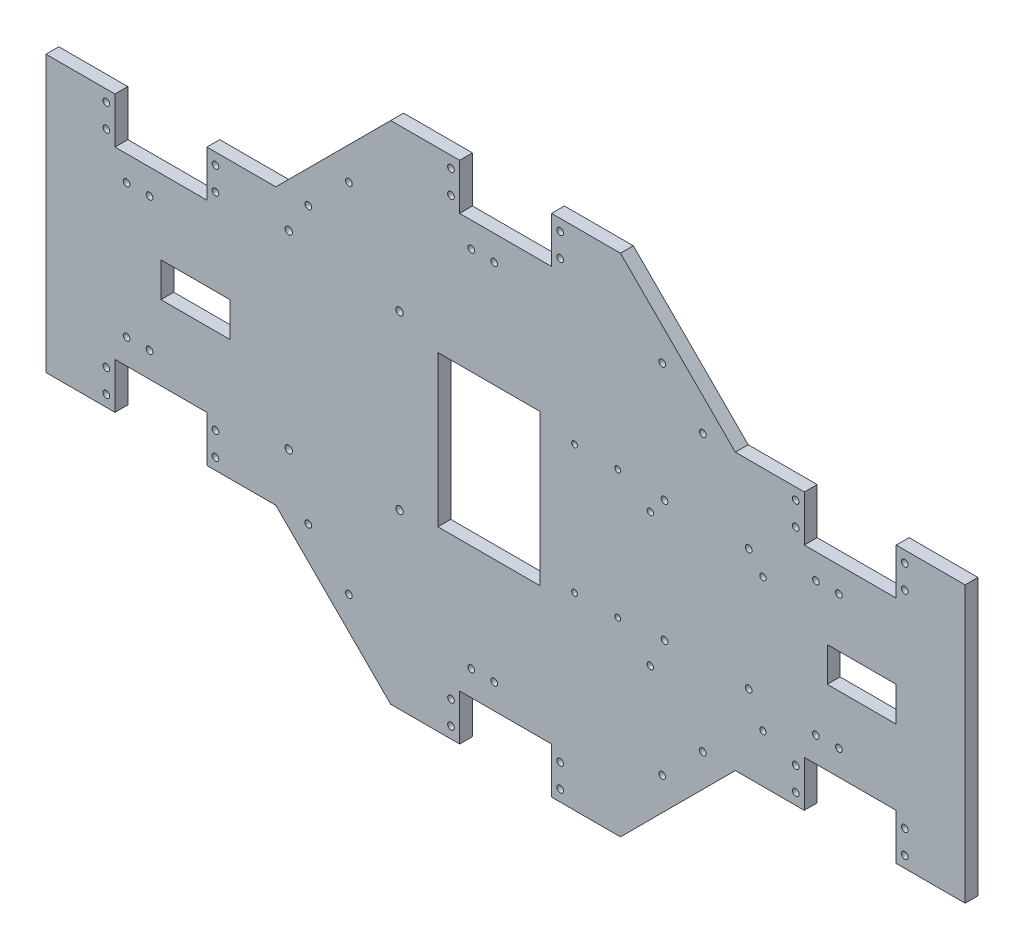
SolidWorks part; units mm, degrees
ref_plane "Front" through (0, 0, 0) normal (0, 0, 1) x (1, 0, 0)
ref_plane "Top" through (0, 0, 0) normal (0, 1, 0) x (1, 0, 0)
ref_plane "Right" through (0, 0, 0) normal (1, 0, 0) x (0, 0, -1)
sketch "Esquisse1" plane through (0, 0, 0) normal (0, 0, 1) x (1, 0, 0)
  line L0 (100, -60) -> (150, -110)
  line L1 (0, 0) -> (25.8386, 0)
  line L2 (0, 0) -> (0, -60)
  line L3 (0, -60) -> (100, -60)
  line L5 (0, 0) -> (100, -60) construction
  line L6 (0, -60) -> (25.8386, 0) construction
  line L7 (150, -110) -> (250, -110)
  line L8 (250, -110) -> (300, -60)
  line L9 (300, -60) -> (400, -60)
  line L10 (400, -60) -> (400, 0)
  line L11 (400, 0) -> (25.8386, 0)
  point P0 (0, 0)
  dimension "D1" = 100
  dimension "D2" = 100
  dimension "D3" = 100
  dimension "D4" = 135
  dimension "D5" = 135
  dimension "D6" = 0
  dimension "D7" = 50
  dimension "D8" = 60
extrude "Boss.-Extru.1" add sketch "Esquisse1" along normal blind 5.6
sketch "Esquisse2" plane through (0, 0, 5.6) normal (0, 0, 1) x (1, 0, 0)
  line L0 (0, -60) -> (100, -60) construction
  line L1 (30, -40) -> (70, -40)
  line L2 (30, -40) -> (30, -60)
  line L3 (30, -60) -> (70, -60)
  line L4 (70, -40) -> (70, -60)
  line L5 (30, -40) -> (70, -60) construction
  line L6 (30, -60) -> (70, -40) construction
  line L7 (0, 0) -> (0, -60) construction
  point P0 (0, -90)
  dimension "D1" = 20
  dimension "D2" = 40
  dimension "D3" = 30
extrude "Enlèv. mat.-Extru.1" cut sketch "Esquisse2" against normal up to next
sketch "Esquisse3" plane through (0, 0, 5.6) normal (0, 0, 1) x (1, 0, 0)
  line L0 (30, -50) -> (70, -50) construction
  line L1 (30, -40) -> (30, -60) construction
  line L2 (70, -60) -> (70, -40) construction
  circle A0 centre (26.25, -55.08) radius 1.45
  circle A1 centre (73.75, -55.08) radius 1.45
  circle A2 centre (73.75, -44.92) radius 1.45
  circle A3 centre (26.25, -44.92) radius 1.45
  circle A4 centre (35.06, -29.09) radius 1.45
  circle A5 centre (45.06, -29.09) radius 1.45
  dimension "D1" = 3.75
  dimension "D2" = 5.08
  dimension "D3" = 47.5
  dimension "D4" = 2.9
  dimension "D5" = 3.75
  dimension "D6" = 2.9
  dimension "D7" = 2.9
  dimension "D8" = 10
  dimension "D9" = 8.81
  dimension "D10" = 15.83
  dimension "D11" = 0
extrude "Enlèv. mat.-Extru.2" cut sketch "Esquisse3" against normal up to next
sketch "Sketch2" plane through (0, 0, 0) normal (0, 0, 1) x (1, 0, 0)
  line L0 (150, -110) -> (250, -110) construction
  line L1 (330, -40) -> (370, -40)
  line L2 (330, -40) -> (330, -60)
  line L3 (330, -60) -> (370, -60)
  line L4 (370, -40) -> (370, -60)
  line L5 (330, -40) -> (370, -60) construction
  line L6 (330, -60) -> (370, -40) construction
  line L7 (300, -60) -> (400, -60) construction
  line L8 (400, -60) -> (400, 0) construction
  line L9 (180, -90) -> (220, -90)
  line L10 (180, -90) -> (180, -110)
  line L11 (180, -110) -> (220, -110)
  line L12 (220, -90) -> (220, -110)
  line L13 (180, -90) -> (220, -110) construction
  line L14 (180, -110) -> (220, -90) construction
  point P0 (0, -90)
  point P11 (-35, 0)
  dimension "D1" = 20
  dimension "D2" = 40
  dimension "D3" = 30
  dimension "D4" = 40
  dimension "D5" = 20
  dimension "D6" = 30
extrude "Cut-Extrude2" cut sketch "Sketch2" against normal through all and the other way through all
sketch "Sketch5" plane through (0, 0, 0) normal (0, 0, 1) x (1, 0, 0)
  line L0 (180, -100) -> (220, -100) construction
  line L1 (220, -110) -> (220, -90) construction
  line L2 (330, -50) -> (370, -50) construction
  line L4 (370, -60) -> (370, -40) construction
  line L5 (330, -40) -> (330, -60) construction
  circle A0 centre (176.25, -105.08) radius 1.45
  circle A1 centre (223.75, -105.08) radius 1.45
  circle A2 centre (223.75, -94.92) radius 1.45
  circle A3 centre (176.25, -94.92) radius 1.45
  circle A4 centre (326.25, -55.08) radius 1.45
  circle A5 centre (373.75, -55.08) radius 1.45
  circle A6 centre (373.75, -44.92) radius 1.45
  circle A7 centre (326.25, -44.92) radius 1.45
  circle A8 centre (185.06, -79.09) radius 1.45
  circle A9 centre (195.06, -79.09) radius 1.45
  circle A10 centre (335.06, -29.09) radius 1.45
  circle A11 centre (345.06, -29.09) radius 1.45
  dimension "D1" = 5.08
  dimension "D2" = 5.08
  dimension "D3" = 47.5
  dimension "D4" = 2.9
  dimension "D5" = 3.75
  dimension "D10" = 2.9
  dimension "D11" = 2.9
  dimension "D12" = 2.9
  dimension "D16" = 2.9
  dimension "D17" = 2.9
  dimension "D6" = 5.08
  dimension "D7" = 5.08
  dimension "D8" = 3.75
  dimension "D9" = 3.75
  dimension "D13" = 10
  dimension "D14" = 8.81
  dimension "D15" = 15.83
  dimension "D18" = 8.81
  dimension "D19" = 15.83
  dimension "D20" = 10
  dimension "D21" = 0
  dimension "D22" = 0
extrude "Cut-Extrude4" cut sketch "Sketch5" along normal through all
mirror "Mirror1" about plane through (0, 0, 0) normal (0, 1, 0) of "Cut-Extrude4", "Cut-Extrude2", "Enlèv. mat.-Extru.1", "Enlèv. mat.-Extru.2", "Boss.-Extru.1"
sketch "Esquisse4" plane through (0, 0, 5.6) normal (0, 0, 1) x (1, 0, 0)
  circle A0 centre (263, -39) radius 1.375
  circle A4 centre (312, -39) radius 1.375
  circle A5 centre (312, 19) radius 1.375
  circle A6 centre (263, 19) radius 1.375
  dimension "D1" = 2.75
  dimension "D2" = 2
  dimension "D3" = 43
  dimension "D4" = 51
  dimension "D5" = 2
extrude "Enlèv. mat.-Extru.4" cut sketch "Esquisse4" against normal through all
sketch "Esquisse6" plane through (0, 0, 0) normal (0, 0, -1) x (-1, 0, 0)
  circle A0 centre (-269.19, -26.31) radius 1.45
  circle A4 centre (-305.82, -26.31) radius 1.45
  circle A5 centre (-305.82, 26.52) radius 1.45
  circle A6 centre (-269.19, 26.52) radius 1.45
  dimension "D1" = 2.9
  dimension "D2" = 2
  dimension "D3" = 63.69
  dimension "D4" = 49.19
  dimension "D5" = 2
extrude "Enlèv. mat.-Extru.6" cut sketch "Esquisse6" against normal through all
sketch "Esquisse8" plane through (0, 0, 0) normal (0, 0, -1) x (-1, 0, 0)
  circle A0 centre (-230, 27.95) radius 1.25
  circle A1 centre (-248.8, 27.95) radius 1.25
  circle A2 centre (-248.8, -27.95) radius 1.25
  circle A3 centre (-230, -27.95) radius 1.25
  dimension "D1" = 2.5
  dimension "D2" = 70
  dimension "D3" = 32.05
  dimension "D4" = 2
  dimension "D5" = 2
extrude "Enlèv. mat.-Extru.7" cut sketch "Esquisse8" against normal through all
sketch "Esquisse9" plane through (0, 0, 0) normal (0, 0, -1) x (-1, 0, 0)
  circle A1 centre (-153.859, -34.88) radius 1.6
  circle A2 centre (-105.639, -36.11) radius 1.6
  circle A3 centre (-105.639, 46.36) radius 1.6
  circle A4 centre (-153.859, 40) radius 1.6
  point P4 (0, 0)
  point P7 (0, 0)
  dimension "D8" = 1.23
  dimension "D1" = 74.88
  dimension "D2" = 82.47
  dimension "D3" = 48.22
  dimension "D4" = 48.22
  dimension "D5" = 48.22
  dimension "D6" = 26.141
  dimension "D7" = 50
extrude "Enlèv. mat.-Extru.8" cut sketch "Esquisse9" against normal through all
sketch "Esquisse10" plane through (0, 0, 0) normal (0, 0, -1) x (-1, 0, 0)
  line L0 (-215, -32.845) -> (-215, 32.845)
  line L1 (-215, 32.845) -> (-170.55, 32.845)
  line L2 (-170.55, 32.845) -> (-170.55, -32.845)
  line L3 (-170.55, -32.845) -> (-215, -32.845)
  dimension "D1" = 44.45
  dimension "D2" = 65.69
  dimension "D3" = 5
  dimension "D4" = 57.155
extrude "Enlèv. mat.-Extru.9" cut sketch "Esquisse10" against normal through all
sketch "Esquisse11" plane through (0, 0, 0) normal (0, 0, -1) x (-1, 0, 0)
  line L1 (-340, 7.5) -> (-370, 7.5)
  line L2 (-340, 7.5) -> (-340, -7.5)
  line L3 (-340, -7.5) -> (-370, -7.5)
  line L4 (-370, 7.5) -> (-370, -7.5)
  line L5 (-50, 7.5) -> (-80, 7.5)
  line L6 (-50, 7.5) -> (-50, -7.5)
  line L7 (-50, -7.5) -> (-80, -7.5)
  line L8 (-80, 7.5) -> (-80, -7.5)
  dimension "D1" = 30
  dimension "D2" = 30
  dimension "D3" = 30
  dimension "D4" = 50
  dimension "D5" = 15
  dimension "D6" = 15
  dimension "D7" = 52.5
  dimension "D8" = 52.5
extrude "Enlèv. mat.-Extru.10" cut sketch "Esquisse11" against normal through all
ref_plane "Plan1" through (200, 0, 0) normal (-1, 0, 0) x (0, 0, 1)
ref_plane "Plan2" through (0, 0, 0) normal (0, 1, 0) x (1, 0, 0)
sketch "Esquisse12" plane through (0, 0, 5.6) normal (0, 0, 1) x (1, 0, 0)
  line L1 (200, 24.0954) -> (200, -24.0954) construction
  line L2 (22.5792, 0) -> (-22.5792, 0) construction
  line L3 (100, 60) -> (150, 110) construction
  circle A0 centre (131.8198, 77.6777) radius 1.45
  circle A1 centre (114.1421, 60) radius 1.45
  circle A2 centre (285.8579, 60) radius 1.45
  circle A3 centre (268.1802, 77.6777) radius 1.45
  circle A4 centre (285.8579, -60) radius 1.45
  circle A5 centre (268.1802, -77.6777) radius 1.45
  circle A6 centre (131.8198, -77.6777) radius 1.45
  circle A7 centre (114.1421, -60) radius 1.45
  dimension "D1" = 2.9
  dimension "D2" = 2.9
  dimension "D3" = 25
  dimension "D4" = 10
  dimension "D5" = 14.1421
  dimension "D6" = 0
extrude "Enlèv. mat.-Extru.11" cut sketch "Esquisse12" against normal through all
